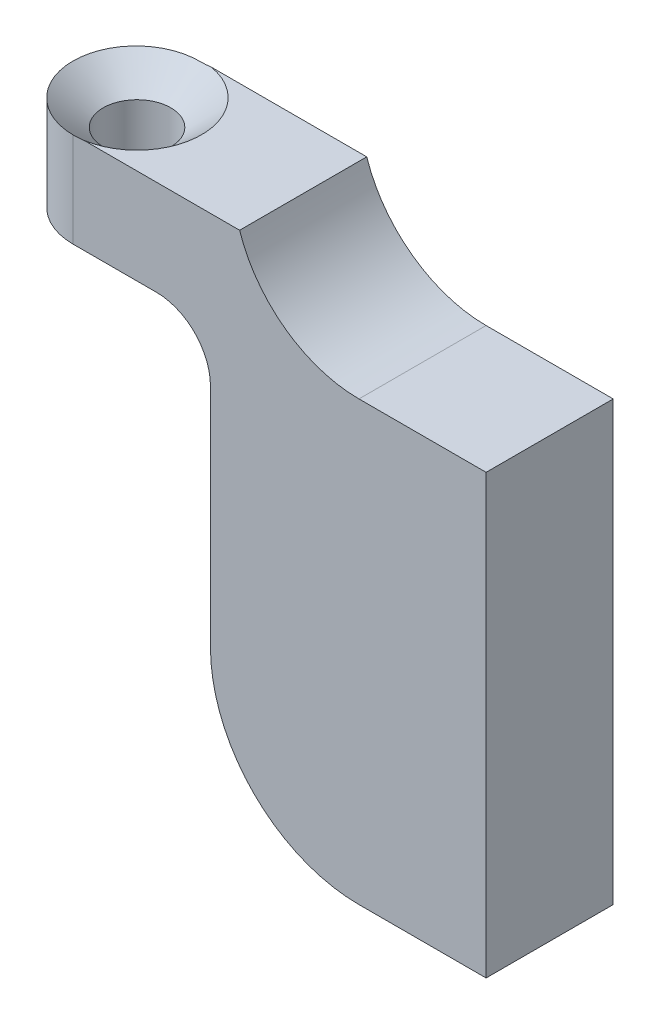
SolidWorks part; units mm, degrees
material "Plain Carbon Steel"
ref_plane "Front Plane" through (0, 0, 0) normal (0, 0, 1) x (1, 0, 0)
ref_plane "Top Plane" through (0, 0, 0) normal (0, 1, 0) x (1, 0, 0)
ref_plane "Right Plane" through (0, 0, 0) normal (1, 0, 0) x (0, 0, -1)
sketch "Sketch1" plane through (0, 0, 0) normal (0, 0, 1) x (1, 0, 0)
  line L0 (0, 0) -> (0, 43.7536)
  line L1 (0, 43.7536) -> (-12.7, 43.7536)
  line L2 (-24.6252, 52.3875) -> (-47.625, 52.3875)
  line L3 (-47.625, 52.3875) -> (-47.625, 42.8625)
  line L4 (-47.625, 42.8625) -> (-32.9358, 42.8625)
  line L5 (0, 0) -> (-12.7, 0)
  line L6 (-27.5404, 14.8404) -> (-27.5404, 37.4671)
  arc A0 (-12.7, 43.7536) -> (-24.6252, 52.3875) centre (-12.7, 56.3061) cw
  arc A3 (-12.7, 0) -> (-27.5404, 14.8404) centre (-12.7, 14.8404) cw
  arc A4 (-27.5404, 37.4671) -> (-32.9358, 42.8625) centre (-32.9358, 37.4671) ccw
  point P13 (-27.0432, 42.8625)
  point P15 (-24.6252, 42.8625)
  point P16 (-32.9358, 39.5393)
  point P17 (-27.5404, 14.8404)
  point P18 (0, 43.7536)
  dimension "D1" = 9.525
  dimension "D4" = 47.625
  dimension "D2" = 12.7
  dimension "D3" = 42.8625
extrude "Boss-Extrude1" add sketch "Sketch1" along normal blind 12.7
sketch "Sketch2" plane through (0, 52.3875, 0) normal (0, 1, 0) x (1, 0, 0)
  line L0 (0, -12.7) -> (0, 0) construction
  point P0 (-41.2242, -6.35)
  dimension "D1" = 41.2242
hole_wizard "CSK for 1/4 Flat Head Machine Screw (100)1" positions "Sketch2" profile "Sketch3" countersink size "1/4" standard "ANSI Inch" end condition through all
sketch "Sketch3" plane through (-41.2242, 52.3875, 6.35) normal (1, 0, 0) x (0, 0, 1)
  line L0 (0, 0) -> (0, 52.3875)
  line L1 (0, 52.3875) -> (3.3782, 52.3875)
  line L2 (3.3782, 52.3875) -> (3.3782, 2.5682)
  line L3 (3.3782, 2.5682) -> (6.4389, 0)
  line L5 (6.4389, 0) -> (0, 0)
  line L6 (-3.3782, 2.5682) -> (-6.4389, 0) construction
  line L11 (0, -6.35) -> (0, 107.95) construction
  dimension "Thru Hole Dia." = 6.7564
  dimension "Thru Hole Depth" = 52.3875
  dimension "Near C'Sink Dia." = 12.8778
  dimension "Near C'Sink Angle" = 100
fillet "Fillet1" 2 edges at (-47.625, 47.625, 12.7) (-47.625, 47.625, 0) type full round first side face at (-26.5024, 35.9335, 12.7) second side face at (-26.5024, 35.9335, 0) middle face at (-47.625, 49.2125, 6.4666)
